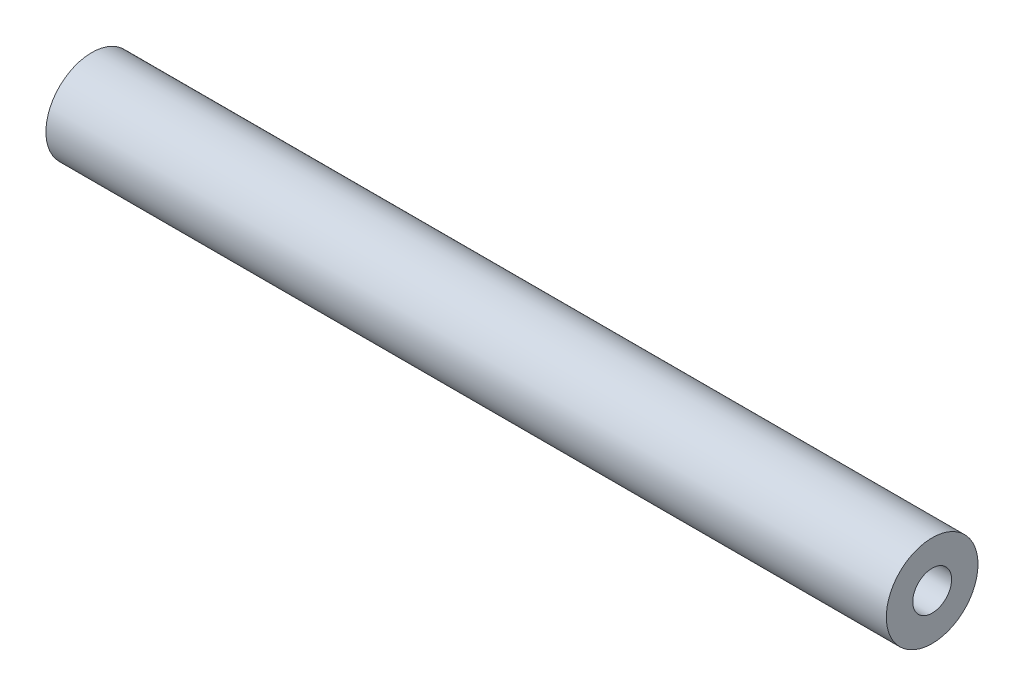
SolidWorks part; units mm, degrees
material "6061-T6 (SS)"
ref_plane "Front Plane" through (0, 0, 0) normal (0, 0, 1) x (1, 0, 0)
ref_plane "Top Plane" through (0, 0, 0) normal (0, 1, 0) x (1, 0, 0)
ref_plane "Right Plane" through (0, 0, 0) normal (1, 0, 0) x (0, 0, -1)
sketch "Sketch1" plane through (0, 0, 0) normal (1, 0, 0) x (0, 0, -1)
  circle A0 centre (0, 0) radius 4.7625
  dimension "D1" = 9.525
extrude "Boss-Extrude1" add sketch "Sketch1" along normal mid plane 87.3125
hole_wizard "#10-32 Tapped Hole1" positions "3DSketch1" profile "Sketch2" tap size "#10-32" standard "ANSI Inch"
sketch3d "3DSketch1"
  line L0 (43.6562, 0, 0) -> (-43.6562, 0, 0) construction
  point P0 (43.6562, 0, 0)
  point P4 (-43.6562, 0, 0)
sketch "Sketch2" plane through (43.6562, 0, 0) normal (0, 1, 0) x (0, 0, -1)
  line L0 (0, 0) -> (0, 17.4693)
  line L1 (0, 17.4693) -> (2.0193, 16.256)
  line L2 (2.0193, 16.256) -> (2.0193, 0)
  line L5 (2.0193, 0) -> (0, 0)
  line L10 (0, 17.4693) -> (-2.0193, 16.256) construction
  line L11 (0, -6.35) -> (0, 107.95) construction
  dimension "Tap Drill Dia." = 4.0386
  dimension "Tap Drill Depth" = 16.256
  dimension "Drill Angle" = 118
cosmetic thread "Hole Thread1"
cosmetic thread "Hole Thread2"
